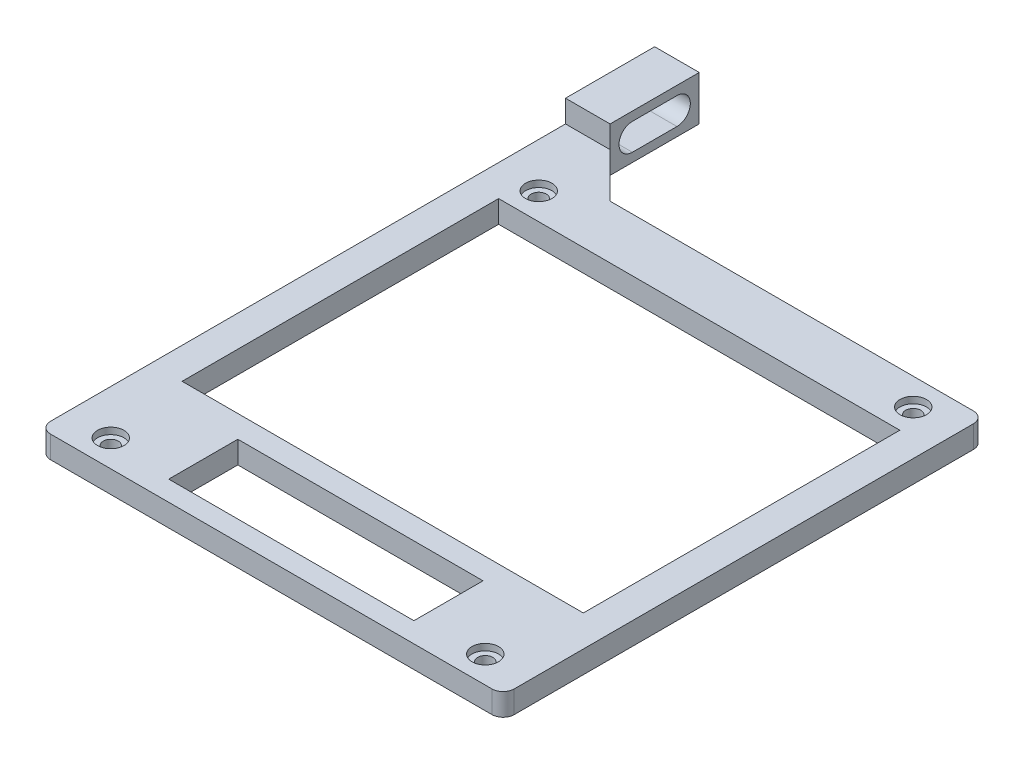
SolidWorks part; units mm, degrees
ref_plane "Front Plane" through (0, 0, 0) normal (0, 0, 1) x (1, 0, 0)
ref_plane "Top Plane" through (0, 0, 0) normal (0, 1, 0) x (1, 0, 0)
ref_plane "Right Plane" through (0, 0, 0) normal (1, 0, 0) x (0, 0, -1)
sketch "Sketch1" plane through (0, 0, 0) normal (0, 1, 0) x (1, 0, 0)
  line L1 (0, 0) -> (132.08, 0)
  line L2 (0, 0) -> (0, 137.16)
  line L3 (0, 137.16) -> (132.08, 137.16)
  line L4 (132.08, 0) -> (132.08, 137.16)
  dimension "D1" = 132.08
  dimension "D2" = 137.16
extrude "Boss-Extrude1" add sketch "Sketch1" along normal blind 6.35
ref_axis "Axis1" through (66.04, 6.35, 0) along (0, 0, -1)
ref_axis "Axis2" through (0, 6.35, -68.58) along (1, 0, 0)
hole_wizard "CBORE for #6 Button Head Cap Screw1" positions "Sketch4" profile "Sketch3" counterbore size "#6" standard "ANSI Inch" end condition up to next
sketch "Sketch4" plane through (0, 6.35, 0) normal (0, 1, 0) x (1, 0, 0)
  line L0 (12.7, 129.54) -> (119.38, 129.54)
  line L1 (119.38, 129.54) -> (119.38, 7.62)
  line L2 (119.38, 7.62) -> (12.7, 7.62)
  line L4 (12.7, 129.54) -> (12.7, 7.62)
  line L7 (66.04, 0) -> (66.04, 137.16) construction
  line L8 (0, 68.58) -> (132.08, 68.58) construction
  point P0 (12.7, 129.54)
  point P2 (119.38, 129.54)
  point P4 (119.38, 7.62)
  point P6 (12.7, 7.62)
  point P28 (66.04, 129.54)
  point P31 (119.38, 68.58)
  dimension "D1" = 106.68
  dimension "D2" = 121.92
sketch "Sketch3" plane through (12.7, 6.35, -129.54) normal (1, 0, 0) x (0, 0, 1)
  line L0 (0, 0) -> (0, 6.35)
  line L1 (0, 6.35) -> (2.1526, 6.35)
  line L3 (2.1526, 6.35) -> (2.1527, 1.8542)
  line L4 (2.1527, 1.8542) -> (3.7706, 1.8542)
  line L5 (3.7706, 1.8542) -> (3.7706, 0)
  line L7 (3.7706, 0) -> (0, 0)
  line L11 (0, -6.35) -> (0, 107.95) construction
  dimension "Thru Hole Dia." = 4.3053
  dimension "Thru Hole Depth" = 6.35
  dimension "C'Bore Dia." = 7.5413
  dimension "C'Bore Depth" = 1.8542
sketch "Sketch5" plane through (0, 6.35, 0) normal (0, 1, 0) x (1, 0, 0)
  line L0 (0, 68.58) -> (132.08, 68.58) construction
  line L1 (8.89, 15.24) -> (123.19, 15.24)
  line L2 (8.89, 15.24) -> (8.89, 121.92)
  line L3 (8.89, 121.92) -> (123.19, 121.92)
  line L4 (123.19, 15.24) -> (123.19, 121.92)
  line L5 (8.89, 15.24) -> (123.19, 121.92) construction
  line L6 (8.89, 121.92) -> (123.19, 15.24) construction
  line L7 (66.04, 0) -> (66.04, 137.16) construction
  point P0 (66.04, 68.58)
  dimension "D1" = 114.3
  dimension "D2" = 106.68
extrude "Cut-Extrude1" cut sketch "Sketch5" against normal through all
sketch "Sketch6" plane through (0, 0, 0) normal (0, -1, 0) x (-1, 0, 0)
  line L1 (0, 137.16) -> (-12.7, 137.16)
  line L2 (0, 137.16) -> (0, 175.26)
  line L3 (0, 175.26) -> (-12.7, 175.26)
  line L4 (-12.7, 137.16) -> (-12.7, 175.26)
  dimension "D1" = 12.7
  dimension "D2" = 38.1
extrude "Boss-Extrude2" add sketch "Sketch6" against normal blind 6.35
sketch "Sketch7" plane through (0, 0, -175.26) normal (0, 0, -1) x (-1, 0, 0)
  line L4 (0, 6.35) -> (-12.7, 6.35)
  line L5 (0, 6.35) -> (0, 12.7)
  line L6 (0, 12.7) -> (-12.7, 12.7)
  line L7 (-12.7, 6.35) -> (-12.7, 12.7)
  dimension "D1" = 6.35
extrude "Boss-Extrude3" add sketch "Sketch7" against normal blind 25.4
sketch "Sketch8" plane through (0, 0, 0) normal (-1, 0, 0) x (0, 0, 1)
  line L0 (-175.26, 6.35) -> (-149.86, 6.35)
  line L1 (-175.26, 12.7) -> (-175.26, 0) construction
  line L3 (-168.91, 6.35) -> (-156.21, 6.35) construction
  line L4 (-168.91, 10.16) -> (-156.21, 10.16)
  line L5 (-168.91, 2.54) -> (-156.21, 2.54)
  arc A0 (-168.91, 10.16) -> (-168.91, 2.54) centre (-168.91, 6.35) ccw
  arc A1 (-156.21, 2.54) -> (-156.21, 10.16) centre (-156.21, 6.35) ccw
  point P8 (-162.56, 6.35)
  dimension "D1" = 3.81
  dimension "D2" = 6.35
extrude "Cut-Extrude2" cut sketch "Sketch8" against normal up to next contours L5 A1 L0 A0 | L0 A1 L4 A0 region at (0, 8.1628, -162.56) region at (0, 4.5372, -162.56)
ref_axis "Axis3" through (12.7, 6.35, -162.56) along (-1, 0, 0)
ref_axis "Axis4" through (12.7, 6.35, -156.21) along (-1, 0, 0)
chamfer "Chamfer1" distance 12.7 angle 45 1 edges at (12.7, 3.175, -137.16)
sketch "Sketch9" plane through (0, 6.35, 0) normal (0, 1, 0) x (1, 0, 0)
  line L7 (66.04, 15.24) -> (66.04, 0) construction
  line L8 (8.89, 15.24) -> (123.19, 15.24) construction
  line L9 (0, 0) -> (132.08, 0) construction
  line L10 (100.965, 15.24) -> (31.115, 15.24)
  line L11 (31.115, 15.24) -> (31.115, 5.715)
  line L12 (31.115, 5.715) -> (100.965, 5.715)
  line L13 (100.965, 15.24) -> (100.965, 5.715)
  point P10 (66.04, 5.715)
  dimension "D1" = 34.925
  dimension "D2" = 9.525
extrude "Cut-Extrude3" cut sketch "Sketch9" against normal up to next
fillet "Fillet1" radius 3.175 3 edges at (132.08, 3.175, -137.16) (132.08, 3.175, 0) (0, 3.175, 0)
sketch "Sketch11" plane through (0, 6.35, 0) normal (0, 1, 0) x (1, 0, 0)
  line L3 (31.115, 5.715) -> (100.965, 5.715) construction
  line L4 (31.115, 15.24) -> (31.115, 5.715) construction
  line L5 (8.89, 15.24) -> (31.115, 15.24)
  line L6 (100.965, 15.24) -> (123.19, 15.24)
  line L7 (100.965, 15.24) -> (100.965, 25.4) construction
  line L8 (31.115, 5.715) -> (100.965, 5.715) construction
  line L9 (31.115, 25.4) -> (31.115, 15.24) construction
  line L10 (31.115, 15.24) -> (100.965, 15.24) construction
  line L11 (31.115, 25.4) -> (100.965, 25.4)
  line L15 (8.89, 121.92) -> (8.89, 15.24) construction
  line L16 (123.19, 15.24) -> (123.19, 121.92) construction
  line L17 (8.89, 31.75) -> (123.19, 31.75)
  line L18 (31.115, 25.4) -> (31.115, 15.24)
  line L19 (100.965, 15.24) -> (100.965, 25.4)
  line L20 (123.19, 15.24) -> (123.19, 31.75)
  line L21 (8.89, 15.24) -> (8.89, 31.75)
  dimension "D1" = 6.35
  dimension "D2" = 10.16
extrude "Boss-Extrude4" add sketch "Sketch11" against normal up to surface (6.35 mm away) up to face at (66.04, 0, -39.5288)
